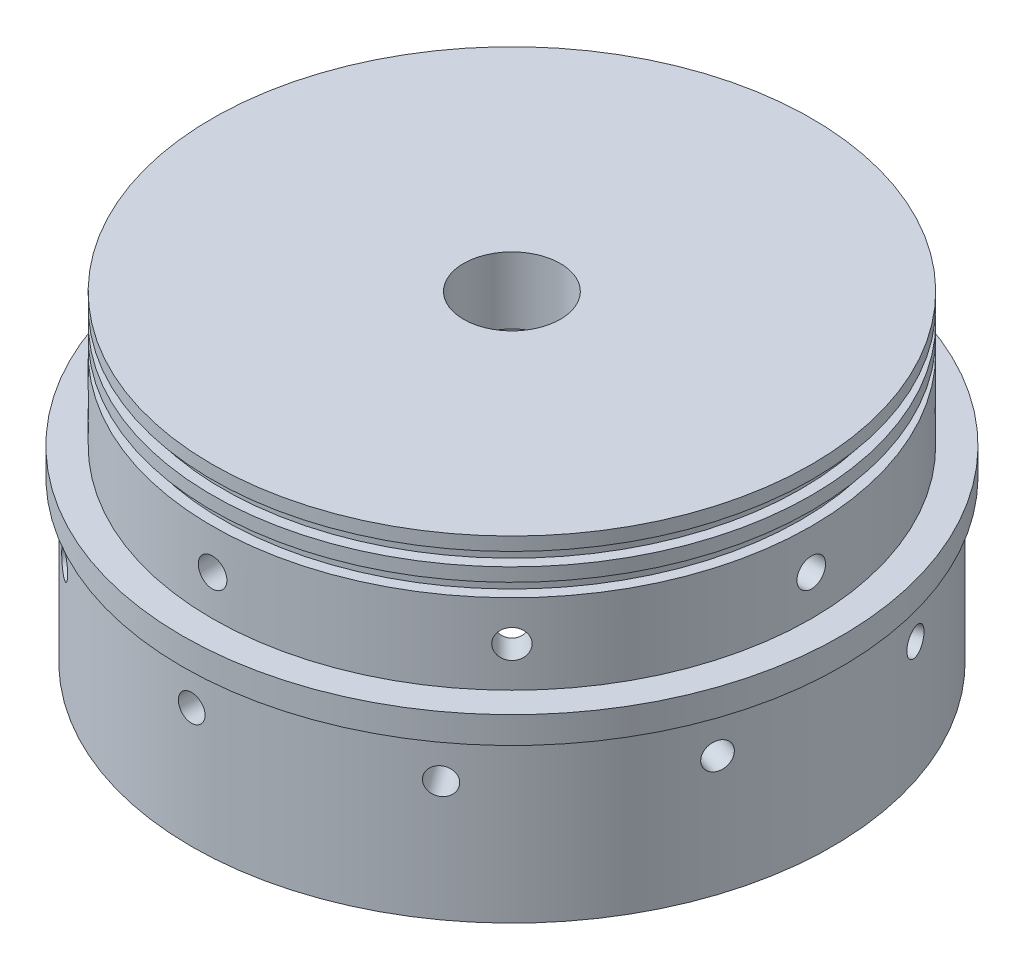
SolidWorks part; units mm, degrees
material "2024-T4"
ref_plane "Front Plane" through (0, 0, 0) normal (0, 0, 1) x (1, 0, 0)
ref_plane "Top Plane" through (0, 0, 0) normal (0, 1, 0) x (1, 0, 0)
ref_plane "Right Plane" through (0, 0, 0) normal (1, 0, 0) x (0, 0, -1)
sketch "Sketch1" plane through (0, 0, 0) normal (0, 1, 0) x (1, 0, 0)
  circle A0 centre (0, 0) radius 78.359
  dimension "D1" = 156.718
extrude "CenterRing(TotOD&Thk)" add sketch "Sketch1" along normal blind 6.35 contours A0 region at (0, 0, 0)
sketch "Sketch2" plane through (0, 6.35, 0) normal (0, 1, 0) x (1, 0, 0)
  circle A0 centre (0, 0) radius 71.247
  dimension "D1" = 142.494
extrude "TankRing(TankID&Ht)" add sketch "Sketch2" along normal blind 31.75
sketch "Sketch3" plane through (0, 0, 0) normal (0, -1, 0) x (1, 0, 0)
  circle A0 centre (0, 0) radius 76.2
  dimension "D1" = 152.4
extrude "FbrGlsRing(FbrGlsID&Ht)" add sketch "Sketch3" along normal blind 38.1
sketch "Sketch4" plane through (0, -38.1, 0) normal (0, -1, 0) x (1, 0, 0)
  circle A0 centre (0, 0) radius 65.0875
  circle A1 centre (0, 0) radius 76.2 construction
  circle A2 centre (0, 0) radius 76.2
  dimension "D1" = 130.175
extrude "Wall&BlkhdThk" cut sketch "Sketch4" against normal offset from surface (60.325 mm away) 15.875 contours A0 up to face at (0, 38.1, 71.247)
sketch "Sketch5" plane through (0, 0, 0) normal (0, 0, 1) x (1, 0, 0)
  line L0 (71.247, 38.1) -> (-71.247, 38.1) construction
  line L1 (-71.247, 38.1) -> (-71.247, 6.35) construction
  line L2 (-71.247, 38.1) -> (-71.247, 6.35)
  line L3 (71.247, 38.1) -> (-71.247, 38.1)
  line L4 (-71.247, 34.925) -> (-68.707, 34.925)
  line L5 (-68.707, 34.925) -> (-68.707, 31.75)
  line L6 (-68.707, 31.75) -> (-71.247, 31.75)
  line L7 (-71.247, 28.575) -> (-68.707, 28.575)
  line L8 (-68.707, 28.575) -> (-68.707, 25.4)
  line L9 (-68.707, 25.4) -> (-71.247, 25.4)
  line L10 (0, 6.35) -> (0, 38.1) construction
  line L11 (78.359, 6.35) -> (-78.359, 6.35) construction
  dimension "D1" = 2.54
  dimension "D2" = 3.175
  dimension "D3" = 3.175
  dimension "D4" = 3.175
  dimension "D5" = 3.175
revolve "O-Ring Channel" cut sketch "Sketch5" angle 360 about L10 region at (-69.977, 33.3375, 0) region at (-69.977, 26.9875, 0)
sketch "Sketch6" plane through (0, 0, 0) normal (0, 0, 1) x (1, 0, 0)
  line L0 (78.359, 6.35) -> (-78.359, 6.35) construction
  line L1 (78.359, 6.35) -> (-78.359, 6.35)
  circle A0 centre (0, 15.875) radius 3.4
  dimension "D1" = 6.8
  dimension "D2" = 9.525
extrude "TankBoltHole" cut sketch "Sketch6" against normal through all contours A0 region at (0, 15.875, 0)
pattern_circular "TankBoltCount" count 8 over 360 about axis through (0, 38.1, 0) along (0, -1, 0) of "TankBoltHole"
sketch "Sketch7" plane through (0, 0, 0) normal (0, 0, 1) x (1, 0, 0)
  line L0 (-76.2, 0) -> (76.2, 0) construction
  line L1 (-76.2, 0) -> (76.2, 0)
  circle A0 centre (0, -9.525) radius 3.175
  dimension "D1" = 6.35
  dimension "D2" = 9.525
extrude "FbrGlsBoltHole" cut sketch "Sketch7" against normal through all contours A0 region at (0, -9.525, 0)
pattern_circular "FbrGlsBoltCount" count 10 over 360 about axis through (0, -38.1, 0) along (0, 1, 0) of "FbrGlsBoltHole" reverse direction yes
sketch "Sketch8" plane through (0, 38.1, 0) normal (0, 1, 0) x (1, 0, 0)
  circle A0 centre (0, 0) radius 11.5094
  dimension "D1" = 23.0188
extrude "3/4NPTFemDrill" cut sketch "Sketch8" against normal through all
fillet "Smoothing" radius 12.7 1 edges at (0, 22.225, 65.0875)
sketch "Sketch9" plane through (0, -38.1, 0) normal (0, -1, 0) x (1, 0, 0)
  circle A0 centre (0, 0) radius 71.4375
  circle A1 centre (0, 0) radius 76.2 construction
  circle A2 centre (0, 0) radius 76.2
  dimension "D1" = 4.7625
extrude "FbrGlsRingTrim" cut sketch "Sketch9" against normal blind 19.05 contours A0
equation "\"D4@Sketch5\"=\"D2@Sketch5\""
equation "\"D5@Sketch5\"=\"D3@Sketch5\""
